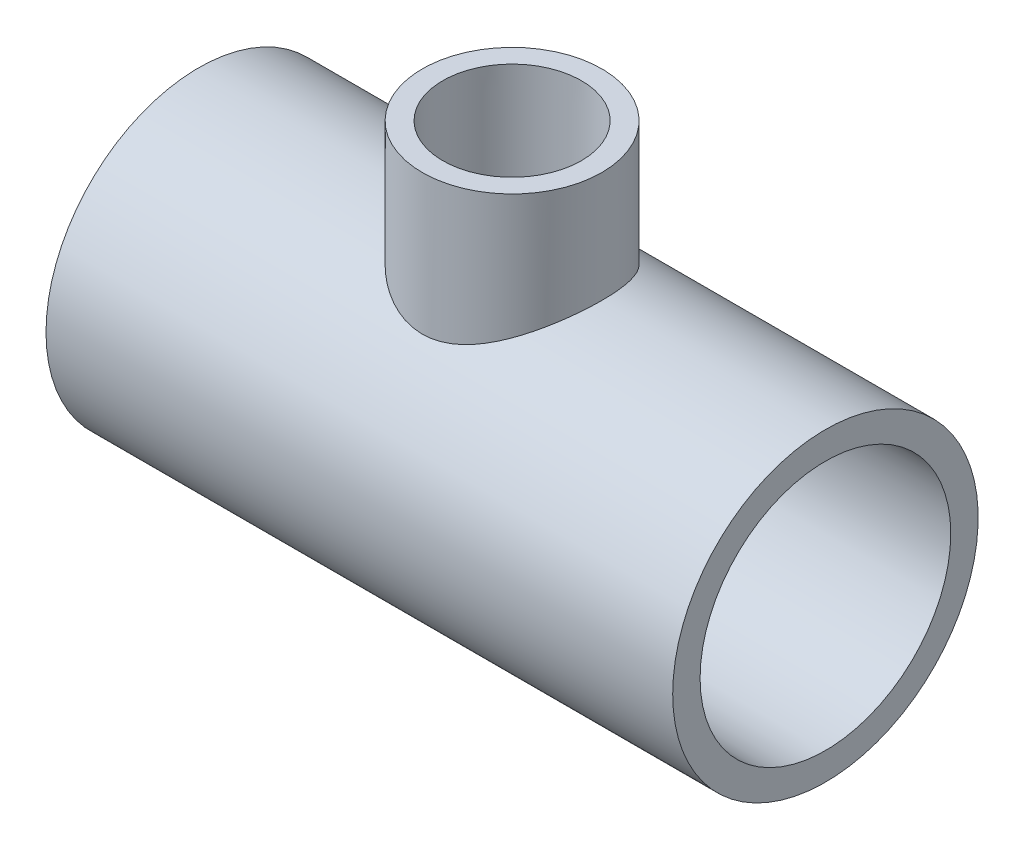
SolidWorks part; units mm, degrees
ref_plane "Front Plane" through (0, 0, 0) normal (0, 0, 1) x (1, 0, 0)
ref_plane "Top Plane" through (0, 0, 0) normal (0, 1, 0) x (1, 0, 0)
ref_plane "Right Plane" through (0, 0, 0) normal (1, 0, 0) x (0, 0, -1)
sketch "Sketch0" plane through (0, 0, 0) normal (0, 0, 1) x (1, 0, 0)
  line L0 (-60.706, 0) -> (0, 0) construction
  line L1 (0, 0) -> (0, 51.054) construction
  line L2 (-25.908, 0) -> (0, 0) construction
  line L3 (0, 0) -> (0, 25.4) construction
  line L4 (-60.706, 29.591) -> (-60.706, -29.591) construction
  line L5 (-25.908, 24.0538) -> (-60.706, 24.2824) construction
  line L6 (-25.908, 24.0538) -> (-25.908, -24.0538) construction
  line L7 (-25.908, -24.0538) -> (-60.706, -24.2824) construction
  line L8 (-60.706, 24.2824) -> (-60.706, -24.2824) construction
  line L9 (-17.399, 51.054) -> (17.399, 51.054) construction
  line L10 (-13.4366, 51.054) -> (13.4366, 51.054) construction
  line L11 (13.4366, 51.054) -> (13.2842, 25.4) construction
  line L12 (13.2842, 25.4) -> (-13.2842, 25.4) construction
  line L13 (-13.2842, 25.4) -> (-13.4366, 51.054) construction
  line L14 (-25.908, 19.05) -> (-25.908, -19.05) construction
  line L15 (-60.706, 0) -> (-25.908, 0) construction
  line L16 (0, 51.054) -> (0, 25.4) construction
  line L17 (0, 0) -> (25.908, 0) construction
  line L18 (-9.4234, 25.4) -> (9.4234, 25.4) construction
  line L19 (25.908, 0) -> (60.706, 0) construction
  dimension "H" = 60.706
  dimension "G" = 25.908
  dimension "M" = 59.182
  dimension "OD A" = 48.5648
  dimension "OD B" = 48.1076
  dimension "ID" = 38.1
  dimension "H3" = 51.054
  dimension "G3" = 25.4
  dimension "M3" = 34.798
  dimension "OD A3" = 26.8732
  dimension "OD B3" = 26.5684
  dimension "ID3" = 18.8468
sketch "Sketch1" plane through (0, 0, 0) normal (0, 0, 1) x (1, 0, 0)
  line L0 (-60.706, 0) -> (0, 0) construction
  line L1 (-60.706, 0) -> (0, 0) construction
  line L2 (0, 0) -> (0, -29.591) construction
  line L3 (-60.706, -29.591) -> (-25.908, -29.591)
  line L4 (-60.706, -29.591) -> (-60.706, -24.2824)
  line L5 (-60.706, -24.2824) -> (-25.908, -24.0538)
  line L6 (-25.908, -29.591) -> (-25.908, -24.0538)
  line L7 (-25.908, -29.591) -> (0, -29.591) construction
  line L8 (60.706, -24.2824) -> (25.908, -24.0538)
  line L9 (60.706, -29.591) -> (60.706, -24.2824)
  line L10 (25.908, -29.591) -> (25.908, -24.0538)
  line L11 (60.706, -29.591) -> (25.908, -29.591)
revolve "Revolve1" add sketch "Sketch1" angle 360 about L1
sketch "Sketch2" plane through (0, 0, 0) normal (0, 0, 1) x (1, 0, 0)
  line L0 (13.4366, 51.054) -> (13.2842, 25.4)
  line L1 (13.2842, 25.4) -> (17.399, 25.4)
  line L2 (17.399, 25.4) -> (17.399, 51.054)
  line L3 (17.399, 51.054) -> (13.4366, 51.054)
  line L4 (0, 0) -> (0, 51.054) construction
  line L5 (0, 0) -> (0, 51.054) construction
revolve "Revolve2" add sketch "Sketch2" angle 360 about L5
sketch "Sketch3" plane through (-25.908, 0, 0) normal (1, 0, 0) x (0, 0, -1)
  circle A0 centre (0, 0) radius 19.05
  circle A1 centre (0, 0) radius 29.591
sketch "Sketch4" plane through (-25.908, 0, 0) normal (1, 0, 0) x (0, 0, -1)
  circle A0 centre (0, 0) radius 29.591 construction
  circle A1 centre (0, 0) radius 29.591
extrude "Boss-Extrude1" add sketch "Sketch4" along normal up to vertex (51.816 mm away) up to point (25.908, 0, 0)
sketch "Sketch5" plane through (0, 25.4, 0) normal (0, -1, 0) x (1, 0, 0)
  circle A0 centre (0, 0) radius 17.399 construction
  circle A1 centre (0, 0) radius 17.399
extrude "Boss-Extrude2" add sketch "Sketch5" along normal up to vertex (25.4 mm away) up to point (0, 0, 0)
sketch "Sketch6" plane through (0, 0, 0) normal (0, 0, 1) x (1, 0, 0)
  line L0 (-60.706, -24.2824) -> (-25.908, -24.0538)
  line L1 (-25.908, -24.0538) -> (-25.908, -19.05)
  line L2 (-25.908, -19.05) -> (25.908, -19.05)
  line L3 (25.908, -24.0538) -> (25.908, 24.0538) construction
  line L4 (0, -19.05) -> (0, 0) construction
  line L5 (25.908, -24.0538) -> (25.908, -19.05)
  line L6 (60.706, -24.2824) -> (60.706, 24.2824) construction
  line L7 (60.706, -29.591) -> (60.706, 29.591) construction
  line L8 (60.706, -24.2824) -> (60.706, 0)
  line L9 (60.706, 0) -> (-60.706, 0)
  line L10 (-60.706, 0) -> (-60.706, -24.2824)
  line L11 (60.706, -24.2824) -> (25.908, -24.0538)
revolve "Cut-Revolve1" cut sketch "Sketch6" angle 360 about L9
sketch "Sketch7" plane through (0, 0, 0) normal (0, 0, 1) x (1, 0, 0)
  line L0 (13.4366, 51.054) -> (13.2842, 25.4)
  line L1 (13.2842, 25.4) -> (9.4234, 25.4)
  line L2 (9.4234, 25.4) -> (9.4234, 0)
  line L3 (0, 0) -> (25.908, 0) construction
  line L4 (9.4234, 0) -> (0, 0)
  line L5 (0, 0) -> (0, 51.054)
  line L6 (-17.399, 51.054) -> (17.399, 51.054) construction
  line L7 (0, 51.054) -> (13.4366, 51.054)
revolve "Cut-Revolve2" cut sketch "Sketch7" angle 360 about L5
other "CPoint1" parameters "Diameter"=38.1, "StubLength"=57.15
ref_axis "Axis1" through (-35.908, 0, 0) along (1, 0, 0)
other "CPoint2" parameters "Diameter"=38.1, "StubLength"=57.15
ref_axis "Axis2" through (35.908, 0, 0) along (-1, 0, 0)
other "CPoint3" parameters "Diameter"=19.05, "StubLength"=57.15
ref_axis "Axis3" through (0, 35.4, 0) along (0, -1, 0)
other "RPoint1"
